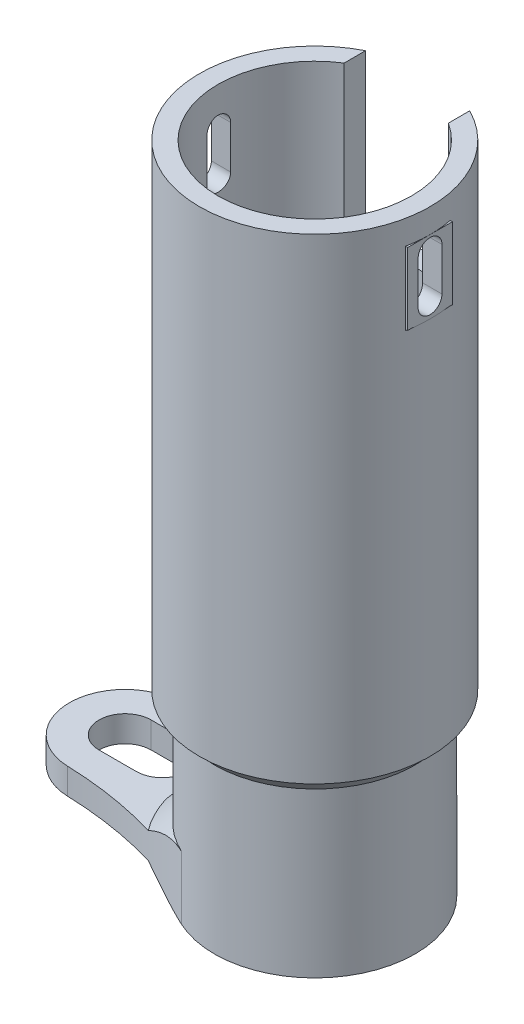
SolidWorks part; units mm, degrees
material "PET"
ref_plane "Спереди" through (0, 0, 0) normal (0, 0, 1) x (1, 0, 0)
ref_plane "Сверху" through (0, 0, 0) normal (0, 1, 0) x (1, 0, 0)
ref_plane "Справа" through (0, 0, 0) normal (1, 0, 0) x (0, 0, -1)
sketch "Эскиз1" plane through (0, 0, 0) normal (0, 1, 0) x (1, 0, 0)
  circle A0 centre (0, 0) radius 10.75
  circle A1 centre (0, 0) radius 13.5
  dimension "D1" = 21.5
  dimension "D2" = 27
extrude "Бобышка-Вытянуть1" add sketch "Эскиз1" along normal blind 22
sketch "Эскиз2" plane through (0, 0, 0) normal (0, -1, 0) x (1, 0, 0)
  circle A0 centre (0, 0) radius 13.5
  circle A1 centre (0, 0) radius 9.25
  dimension "D1" = 18.5
extrude "Бобышка-Вытянуть2" add sketch "Эскиз2" along normal blind 2
sketch "Эскиз3" plane through (0, 22, 0) normal (0, 1, 0) x (1, 0, 0)
  circle A0 centre (0, 0) radius 13
  circle A1 centre (0, 0) radius 15.5
  dimension "D1" = 26
  dimension "D2" = 31
extrude "Бобышка-Вытянуть3" add sketch "Эскиз3" along normal blind 43
sketch "Эскиз4" plane through (0, 65, 0) normal (0, 1, 0) x (1, 0, 0)
  line L0 (0, 16.5717) -> (0, -16.8589) construction
  line L1 (-7, 13.8293) -> (-7, 10.9545)
  line L2 (7, 13.8293) -> (7, 10.9545)
  arc A0 (-7, 13.8293) -> (7, 13.8293) centre (0, 0) ccw
  arc A1 (-7, 10.9545) -> (7, 10.9545) centre (0, 0) ccw
  dimension "D1" = 26
  dimension "D2" = 31
  dimension "D3" = 7
extrude "Бобышка-Вытянуть4" add sketch "Эскиз4" along normal blind 21
sketch "Эскиз5" plane through (0, 0, 0) normal (0, 0, 1) x (1, 0, 0)
  line L1 (0, 81.2342) -> (0, 75.3024) construction
  line L2 (1.6, 81.2342) -> (1.6, 75.3024)
  line L3 (-1.6, 81.2342) -> (-1.6, 75.3024)
  arc A1 (1.6, 81.2342) -> (-1.6, 81.2342) centre (0, 81.2342) ccw
  arc A2 (-1.6, 75.3024) -> (1.6, 75.3024) centre (0, 75.3024) ccw
  point P7 (0, 78.2683)
  dimension "D2" = 1.6
sketch "Эскиз6" plane through (0, 0, 0) normal (1, 0, 0) x (0, 0, -1)
  line L0 (0, 80.3024) -> (0, 75.3024) construction
  line L1 (0, 81.2342) -> (0, 75.3024) construction
  line L2 (1.6, 80.3024) -> (1.6, 75.3024)
  line L3 (-1.6, 80.3024) -> (-1.6, 75.3024)
  arc A0 (1.6, 80.3024) -> (-1.6, 80.3024) centre (0, 80.3024) ccw
  arc A1 (-1.6, 75.3024) -> (1.6, 75.3024) centre (0, 75.3024) ccw
  point P5 (0, 77.8024)
  dimension "D1" = 1.6
  dimension "D2" = 5
extrude "Вырез-Вытянуть2" cut sketch "Эскиз6" against normal through all both and the other way through all
chamfer "Фаска1" distance 2 angle 38 1 edges at (0, 22, 13.5) first distance on face at (0, 22, 13.5)
sketch "Эскиз7" plane through (0, 0, 0) normal (1, 0, 0) x (0, 0, -1)
  line L0 (0, 81.2342) -> (0, 75.3024) construction
  line L2 (3, 73.0905) -> (-3, 73.0905)
  line L3 (3, 73.0905) -> (3, 82.7549)
  line L4 (3, 82.7549) -> (-3, 82.7549)
  line L5 (-3, 73.0905) -> (-3, 82.7549)
  line L6 (3, 73.0905) -> (-3, 82.7549) construction
  line L7 (3, 82.7549) -> (-3, 73.0905) construction
  point P2 (0, 77.9227)
  dimension "D1" = 6
  dimension "D2" = 9.6644
extrude "Бобышка-Вытянуть5" add sketch "Эскиз7" along normal blind 15.5 and the other way blind 15.5
sketch "Эскиз8" plane through (0, 86, 0) normal (0, 1, 0) x (1, 0, 0)
  circle A0 centre (0, 0) radius 13
extrude "Вырез-Вытянуть3" cut sketch "Эскиз8" against normal blind 15
sketch "Эскиз9" plane through (-15.5, 0, 0) normal (-1, 0, 0) x (0, 0, 1)
  line L0 (0, 80.8089) -> (0, 75.0364) construction
  line L1 (0, 81.2342) -> (0, 82.8342) construction
  line L2 (0, 81.2342) -> (0, 75.3024) construction
  line L3 (0, 73.7024) -> (0, 75.3024) construction
  line L4 (1.6, 80.8089) -> (1.6, 75.0364)
  line L5 (-1.6, 80.8089) -> (-1.6, 75.0364)
  line L6 (-3, 77.9227) -> (3, 77.9227) construction
  line L7 (-3, 73.0905) -> (-3, 82.7549) construction
  line L8 (3, 82.7549) -> (3, 73.0905) construction
  arc A0 (1.6, 80.8089) -> (-1.6, 80.8089) centre (0, 80.8089) ccw
  arc A1 (-1.6, 75.0364) -> (1.6, 75.0364) centre (0, 75.0364) ccw
  point P8 (0, 77.9227)
  dimension "D1" = 1.6
extrude "Вырез-Вытянуть4" cut sketch "Эскиз9" against normal blind 55
chamfer "Фаска3" distance 0.2 angle 38 2 edges at (-15.4266, 73.0905, -1.5071) (-15.4266, 73.0905, 1.5071) first distance on face at (-15.4267, 73.0905, -2.0024) first distance on face at (-15.4267, 73.0905, 2.0024)
chamfer "Фаска4" distance 0.2 angle 38 2 edges at (15.4266, 73.0905, 1.5071) (15.4266, 73.0905, -1.5071) first distance on face at (15.4267, 73.0905, 2.0024) first distance on face at (15.4267, 73.0905, -2.0024)
sketch "Эскиз10" plane through (0, -2, 0) normal (0, -1, 0) x (1, 0, 0)
  line L0 (0, 0) -> (-26.5, 0) construction
  line L1 (-20.5, 0) -> (-25.5, 0) construction
  line L2 (-20.5, -3.5) -> (-25.5, -3.5)
  line L3 (-20.5, 3.5) -> (-25.5, 3.5)
  line L4 (-25.5, -7.5) -> (-11.225, -7.5)
  line L5 (-25.5, 7.5) -> (-11.225, 7.5)
  circle A0 centre (0, 0) radius 13.5 construction
  circle A1 centre (0, 0) radius 13.5
  arc A2 (-11.225, 7.5) -> (-11.225, -7.5) centre (0, 0) ccw
  arc A3 (-11.225, 7.5) -> (-11.225, -7.5) centre (0, 0) ccw
  arc A4 (-20.5, -3.5) -> (-20.5, 3.5) centre (-20.5, 0) ccw
  arc A5 (-25.5, 3.5) -> (-25.5, -3.5) centre (-25.5, 0) ccw
  arc A6 (-25.5, 7.5) -> (-25.5, -7.5) centre (-25.5, 0) ccw
  point P8 (-23, 0)
  circle M8 centre (0, 0) radius 13.5
  dimension "D2" = 3.5
  dimension "D3" = 20.5
  dimension "D6" = 15
  dimension "D4" = 6
  dimension "D5" = 5
  dimension "D1" = 0
extrude "Бобышка-Вытянуть6" add sketch "Эскиз10" against normal blind 6 contours L5 A6 L4 A5 L3 A4 L2 M8 region at (-32.7356, -2, 0)
sketch "Эскиз11" plane through (0, -2, 0) normal (0, -1, 0) x (1, 0, 0)
  line L2 (-11.225, 7.5) -> (-25.5, 7.5)
  line L3 (-25.5, -7.5) -> (-11.225, -7.5)
  line L4 (-11.225, 7.5) -> (-25.5, 7.5)
  line L5 (-25.5, -7.5) -> (-11.225, -7.5)
  arc A2 (-11.225, -7.5) -> (-11.225, 7.5) centre (0, 0) ccw
  arc A3 (-25.5, 7.5) -> (-25.5, -7.5) centre (-25.5, 0) ccw
  arc A5 (-25.5, 7.5) -> (-25.5, -7.5) centre (-25.5, 0) ccw
  arc A8 (-11.225, 7.5) -> (-11.225, -7.5) centre (0, 0) ccw
  dimension "D1" = 0
extrude "Вырез-Вытянуть5" cut sketch "Эскиз11" against normal blind 2.5
fillet "Скругление1" radius 51.5 2 edges at (-11.225, 2.25, -7.5) (-11.225, 2.25, 7.5)
chamfer "Фаска5" distance 2.5 angle 45 1 edges at (-13.5, 0.5, 0)
chamfer "Фаска6" distance 2.5 angle 45 1 edges at (-13.5, 4, 0)
sketch "Эскиз12" plane through (0, 4, 0) normal (0, 1, 0) x (1, 0, 0)
  arc A0 (-20.5, -3.5) -> (-20.5, 3.5) centre (-20.5, 0) ccw construction
  arc A1 (-20.5, -3.5) -> (-20.5, 3.5) centre (-20.5, 0) ccw
  circle A2 centre (-20.5, 0) radius 7
  dimension "D1" = 14
extrude "Вырез-Вытянуть6" cut sketch "Эскиз12" along normal blind 12.5 contours A2
sketch "Эскиз13" plane through (0, 0.5, 0) normal (0, -1, 0) x (1, 0, 0)
  line L0 (-21.7193, -6.9795) -> (-21.494, -6.9291)
  circle A2 centre (-20.5, 0) radius 7
  arc M3 (-12.8326, -9.5564) -> (-12.8326, 9.5564) centre (0, 0) cw
  arc M6 (-25.5, -3.5) -> (-25.5, 3.5) centre (-25.5, 0) cw
  line M7 (-25.5, 3.5) -> (-20.5, 3.5)
  arc M8 (-20.5, 3.5) -> (-20.5, -3.5) centre (-20.5, 0) cw
  line M9 (-20.5, -3.5) -> (-25.5, -3.5)
  dimension "D1" = 14
extrude "Вырез-Вытянуть7" cut sketch "Эскиз13" along normal blind 12.5 contours A2 M6 M9 M8 M7 | A2 M3 M6 M7 M8 M9 | A2 M3 region at (-14.8489, 0.5, 0) region at (-16.1804, 0.5, 0) region at (-22.4375, 0.5, 0)
sketch "Эскиз16" plane through (0, -2, 0) normal (0, -1, 0) x (1, 0, 0)
  circle A0 centre (0, 0) radius 9.25
